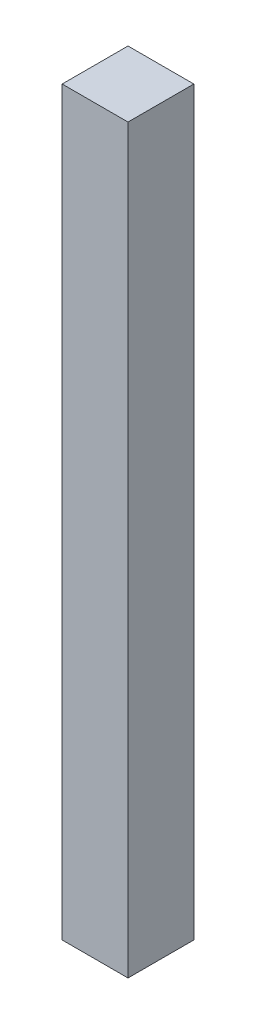
SolidWorks part; units mm, degrees
ref_plane "Front Plane" through (0, 0, 0) normal (0, 0, 1) x (1, 0, 0)
ref_plane "Top Plane" through (0, 0, 0) normal (0, 1, 0) x (1, 0, 0)
ref_plane "Right Plane" through (0, 0, 0) normal (1, 0, 0) x (0, 0, -1)
sketch "Sketch1" plane through (0, 0, 0) normal (0, 1, 0) x (1, 0, 0)
  line L1 (0, 0) -> (25.4, 0)
  line L2 (0, 0) -> (0, 25.4)
  line L3 (0, 25.4) -> (25.4, 25.4)
  line L4 (25.4, 0) -> (25.4, 25.4)
  dimension "D1" = 25.4
  dimension "D2" = 25.4
extrude "Boss-Extrude1" add sketch "Sketch1" along normal blind 609.6
sketch "Sketch3" plane through (0, 0, -25.4) normal (0, 0, -1) x (-1, 0, 0)
  line L0 (0, 609.6) -> (0, 0) construction
  line L1 (0, 466.3042) -> (-25.4, 466.3042)
  line L2 (0, 466.3042) -> (0, 609.6)
  line L3 (0, 609.6) -> (-25.4, 609.6)
  line L4 (-25.4, 466.3042) -> (-25.4, 609.6)
  line L6 (-25.4, 466.3042) -> (0, 466.3042) construction
extrude "Cut-Extrude1" [suppressed] cut sketch "Sketch3" against normal up to surface (25.4 mm away) up to face at (12.7, 304.8, 0)
sketch "Sketch4" [suppressed] plane through (0, 0, 0) normal (0, 0, 1) x (1, 0, 0)
  line L0 (0, 609.6) -> (0, 0) construction
  line L1 (0, 276.4933) -> (25.4, 276.4933)
  line L2 (0, 276.4933) -> (0, 609.6)
  line L3 (0, 609.6) -> (25.4, 609.6)
  line L4 (25.4, 276.4933) -> (25.4, 609.6)
  line L6 (0, 276.4933) -> (25.4, 276.4933) construction
extrude "Cut-Extrude2" [suppressed] cut sketch "Sketch4" against normal up to surface (430.6021 mm away) up to face at (12.7, 304.8, -25.4)
sketch "Sketch5" plane through (0, 0, -25.4) normal (0, 0, -1) x (-1, 0, 0)
  line L0 (0, 609.6) -> (0, 0) construction
  line L1 (0, 571.9407) -> (-25.4, 571.9407)
  line L2 (0, 571.9407) -> (0, 609.6)
  line L3 (0, 609.6) -> (-25.4, 609.6)
  line L4 (-25.4, 571.9407) -> (-25.4, 609.6)
extrude "Cut-Extrude3" cut sketch "Sketch5" against normal up to surface (25.4 mm away) up to face at (12.7, 304.8, 0)
sketch "Sketch6" [suppressed] plane through (0, 0, -25.4) normal (0, 0, -1) x (-1, 0, 0)
  line L0 (0, 609.6) -> (0, 0) construction
  line L1 (0, 553.696) -> (-25.4, 553.696)
  line L2 (0, 553.696) -> (0, 609.6)
  line L3 (0, 609.6) -> (-25.4, 609.6)
  line L4 (-25.4, 553.696) -> (-25.4, 609.6)
  line L6 (-25.4, 553.696) -> (0, 553.696) construction
extrude "Cut-Extrude4" [suppressed] cut sketch "Sketch6" against normal up to surface (25.4 mm away) up to face at (12.7, 285.9703, 0)
sketch "Sketch7" [suppressed] plane through (0, 0, 0) normal (0, 0, 1) x (1, 0, 0)
  line L0 (25.4, 609.6) -> (25.4, 0) construction
  line L1 (25.4, 422.1079) -> (0, 422.1079)
  line L2 (25.4, 422.1079) -> (25.4, 609.6)
  line L3 (25.4, 609.6) -> (0, 609.6)
  line L4 (0, 422.1079) -> (0, 609.6)
  line L8 (0, 422.1079) -> (25.4, 422.1079) construction
extrude "Cut-Extrude5" [suppressed] cut sketch "Sketch7" against normal up to surface (25.4 mm away) up to face at (12.7, 285.9703, -25.4)
sketch "Sketch8" [suppressed] plane through (0, 0, -25.4) normal (0, 0, -1) x (-1, 0, 0)
  line L0 (0, 609.6) -> (0, 0) construction
  line L1 (0, 319.3022) -> (-25.4, 319.3022)
  line L2 (0, 319.3022) -> (0, 609.6)
  line L3 (0, 609.6) -> (-25.4, 609.6)
  line L4 (-25.4, 319.3022) -> (-25.4, 609.6)
  line L6 (-25.4, 319.3022) -> (0, 319.3022) construction
extrude "Cut-Extrude6" [suppressed] cut sketch "Sketch8" against normal up to surface (25.4 mm away) up to face at (12.7, 285.9703, 0)
sketch "Sketch9" [suppressed] plane through (0, 0, 0) normal (0, 0, 1) x (1, 0, 0)
  line L0 (0, 609.6) -> (0, 0) construction
  line L1 (0, 329.8783) -> (25.4, 329.8783)
  line L2 (0, 329.8783) -> (0, 609.6)
  line L3 (0, 609.6) -> (25.4, 609.6)
  line L4 (25.4, 329.8783) -> (25.4, 609.6)
  line L6 (0, 329.8783) -> (25.4, 329.8783) construction
extrude "Cut-Extrude7" [suppressed] cut sketch "Sketch9" against normal up to surface (25.4 mm away) up to face at (12.7, 285.9703, -25.4)
sketch "Sketch10" [suppressed] plane through (25.4, 0, 0) normal (1, 0, 0) x (0, 0, -1)
  line L1 (25.4, 329.8783) -> (0, 329.8783)
  line L2 (25.4, 329.8783) -> (25.4, 0)
  line L3 (25.4, 0) -> (0, 0)
  line L4 (0, 329.8783) -> (0, 0)
extrude "Boss-Extrude2" [suppressed] add sketch "Sketch10" along normal blind 25.4
sketch "Sketch11" [suppressed] plane through (0, 0, -25.4) normal (0, 0, -1) x (-1, 0, 0)
  line L1 (0, 329.8783) -> (-50.8, 329.8783)
  line L2 (0, 329.8783) -> (0, 0)
  line L3 (0, 0) -> (-50.8, 0)
  line L4 (-50.8, 329.8783) -> (-50.8, 0)
extrude "Boss-Extrude3" [suppressed] add sketch "Sketch11" along normal blind 25.4
sketch "Sketch12" [suppressed] plane through (0, 0, 0) normal (0, 0, 1) x (1, 0, 0)
  line L1 (25.4, 319.3022) -> (0, 319.3022)
  line L2 (25.4, 319.3022) -> (25.4, 0)
  line L3 (25.4, 0) -> (0, 0)
  line L4 (0, 319.3022) -> (0, 0)
extrude "Boss-Extrude4" [suppressed] add sketch "Sketch12" along normal blind 25.4
sketch "Sketch13" [suppressed] plane through (25.4, 0, 0) normal (1, 0, 0) x (0, 0, -1)
  line L0 (-25.4, 0) -> (25.4, 0) construction
  line L1 (25.4, 319.3022) -> (-25.4, 319.3022)
  line L2 (25.4, 319.3022) -> (25.4, 0)
  line L3 (25.4, 0) -> (-25.4, 0)
  line L4 (-25.4, 319.3022) -> (-25.4, 0)
  line L5 (-25.4, 0) -> (-25.4, 319.3022) construction
extrude "Boss-Extrude5" [suppressed] add sketch "Sketch13" along normal blind 25.4
sketch "Sketch14" [suppressed] plane through (0, 0, -25.4) normal (0, 0, -1) x (-1, 0, 0)
  line L0 (-25.4, 422.1079) -> (-25.4, 0) construction
  line L1 (-25.4, 422.1079) -> (0, 422.1079)
  line L2 (-25.4, 422.1079) -> (-25.4, 0)
  line L3 (-25.4, 0) -> (0, 0)
  line L4 (0, 422.1079) -> (0, 0)
extrude "Boss-Extrude6" [suppressed] add sketch "Sketch14" along normal blind 25.4
sketch "Sketch15" [suppressed] plane through (25.4, 0, 0) normal (1, 0, 0) x (0, 0, -1)
  line L1 (50.8, 422.1079) -> (0, 422.1079)
  line L2 (50.8, 422.1079) -> (50.8, 0)
  line L3 (50.8, 0) -> (0, 0)
  line L4 (0, 422.1079) -> (0, 0)
extrude "Boss-Extrude7" [suppressed] add sketch "Sketch15" along normal blind 25.4
sketch "Sketch16" plane through (0, 0, 0) normal (0, 0, 1) x (1, 0, 0)
  line L1 (25.4, 571.9407) -> (0, 571.9407)
  line L2 (25.4, 571.9407) -> (25.4, 0)
  line L3 (25.4, 0) -> (0, 0)
  line L4 (0, 571.9407) -> (0, 0)
extrude "Boss-Extrude8" add sketch "Sketch16" along normal blind 25.4
sketch "Sketch17" plane through (25.4, 0, 0) normal (1, 0, 0) x (0, 0, -1)
  line L1 (25.4, 571.9407) -> (-25.4, 571.9407)
  line L2 (25.4, 571.9407) -> (25.4, 0)
  line L3 (25.4, 0) -> (-25.4, 0)
  line L4 (-25.4, 571.9407) -> (-25.4, 0)
extrude "Boss-Extrude9" add sketch "Sketch17" along normal blind 25.4
sketch "Sketch18" [suppressed] plane through (0, 0, -25.4) normal (0, 0, -1) x (-1, 0, 0)
  line L1 (0, 276.4933) -> (-25.4, 276.4933)
  line L2 (0, 276.4933) -> (0, 0)
  line L3 (0, 0) -> (-25.4, 0)
  line L4 (-25.4, 276.4933) -> (-25.4, 0)
extrude "Boss-Extrude10" [suppressed] add sketch "Sketch18" along normal blind 25.4
sketch "Sketch19" [suppressed] plane through (25.4, 0, 0) normal (1, 0, 0) x (0, 0, -1)
  line L1 (50.8, 276.4933) -> (0, 276.4933)
  line L2 (50.8, 276.4933) -> (50.8, 0)
  line L3 (50.8, 0) -> (0, 0)
  line L4 (0, 276.4933) -> (0, 0)
extrude "Boss-Extrude11" [suppressed] add sketch "Sketch19" along normal blind 25.4
sketch "Sketch22" [suppressed] plane through (25.4, 0, 0) normal (1, 0, 0) x (0, 0, -1)
  line L1 (0, 553.696) -> (25.4, 553.696)
  line L2 (0, 553.696) -> (0, 0)
  line L3 (0, 0) -> (25.4, 0)
  line L4 (25.4, 553.696) -> (25.4, 0)
extrude "Boss-Extrude14" [suppressed] add sketch "Sketch22" along normal blind 25.4
sketch "Sketch23" [suppressed] plane through (0, 0, -25.4) normal (0, 0, -1) x (-1, 0, 0)
  line L1 (-50.8, 553.696) -> (0, 553.696)
  line L2 (-50.8, 553.696) -> (-50.8, 0)
  line L3 (-50.8, 0) -> (0, 0)
  line L4 (0, 553.696) -> (0, 0)
extrude "Boss-Extrude15" [suppressed] add sketch "Sketch23" along normal blind 25.4
